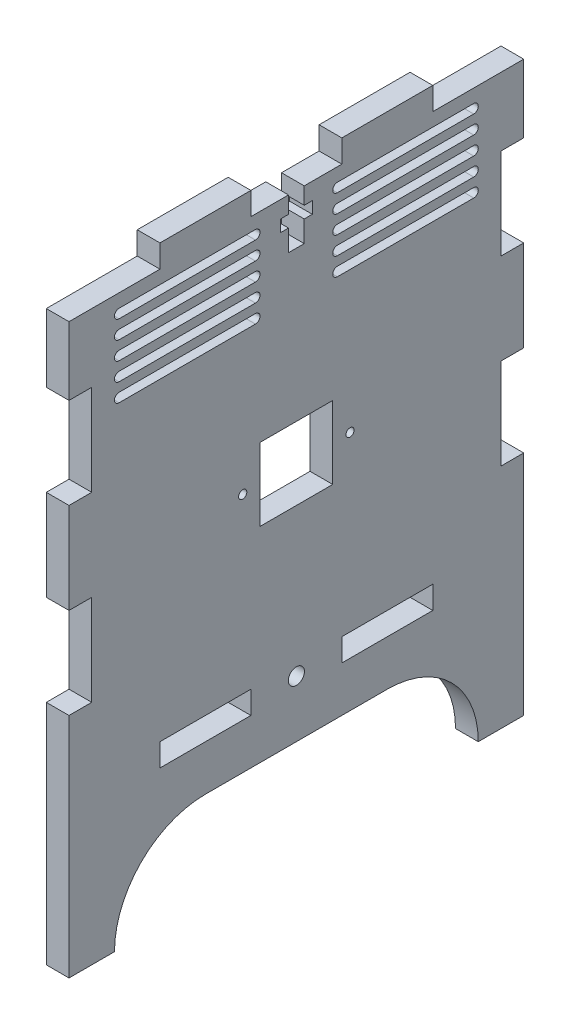
SolidWorks part; units mm, degrees
ref_plane "Front Plane" through (0, 0, 0) normal (0, 0, 1) x (1, 0, 0)
ref_plane "Top Plane" through (0, 0, 0) normal (0, 1, 0) x (1, 0, 0)
ref_plane "Right Plane" through (0, 0, 0) normal (1, 0, 0) x (0, 0, -1)
sketch "Sketch1" plane through (0, 0, 0) normal (1, 0, 0) x (0, 0, -1)
  line L1 (-63.5, 82.55) -> (63.5, 82.55)
  line L2 (-63.5, 82.55) -> (-63.5, -82.55)
  line L3 (-63.5, -82.55) -> (63.5, -82.55)
  line L4 (63.5, 82.55) -> (63.5, -82.55)
  line L5 (-63.5, 82.55) -> (63.5, -82.55) construction
  line L6 (-63.5, -82.55) -> (63.5, 82.55) construction
  point P0 (0, 0)
  dimension "D1" = 127
  dimension "D2" = 165.1
extrude "Boss-Extrude1" add sketch "Sketch1" along normal blind 6.35
sketch "Sketch2" plane through (6.35, 0, 0) normal (1, 0, 0) x (0, 0, -1)
  line L1 (-63.5, 82.55) -> (-38.1, 82.55)
  line L2 (-63.5, 82.55) -> (-63.5, 76.2)
  line L3 (-63.5, 76.2) -> (-38.1, 76.2)
  line L4 (-38.1, 82.55) -> (-38.1, 76.2)
  dimension "D1" = 25.4
  dimension "D2" = 6.35
extrude "Cut-Extrude1" cut sketch "Sketch2" against normal blind 6.35
pattern_linear "LPattern1" count 3 spacing 50.8 along (0, 0, -1) of "Cut-Extrude1"
sketch "Sketch5" plane through (6.35, 0, 0) normal (1, 0, 0) x (0, 0, -1)
  line L0 (-25.4, -82.55) -> (25.4, -82.55) construction
  line L1 (-63.5, -82.55) -> (63.5, -82.55) construction
  line L2 (-25.4, -57.15) -> (25.4, -57.15)
  line L3 (-25.4, -107.95) -> (25.4, -107.95)
  arc A0 (-25.4, -57.15) -> (-25.4, -107.95) centre (-25.4, -82.55) ccw
  arc A1 (25.4, -107.95) -> (25.4, -57.15) centre (25.4, -82.55) ccw
  point P4 (0, -82.55)
  dimension "D2" = 25.4
  dimension "D1" = 50.8
extrude "Cut-Extrude4" cut sketch "Sketch5" against normal blind 6.35
sketch "Sketch8" plane through (6.35, 0, 0) normal (1, 0, 0) x (0, 0, -1)
  line L0 (63.5, -82.55) -> (63.5, 76.2) construction
  line L1 (63.5, 57.15) -> (57.15, 57.15)
  line L2 (63.5, 57.15) -> (63.5, 31.75)
  line L3 (63.5, 31.75) -> (57.15, 31.75)
  line L4 (57.15, 57.15) -> (57.15, 31.75)
  line L5 (38.1, 82.55) -> (12.7, 82.55) construction
  dimension "D1" = 25.4
  dimension "D2" = 25.4
  dimension "D3" = 6.35
extrude "Cut-Extrude6" cut sketch "Sketch8" against normal blind 6.35
pattern_linear "LPattern4" count 2 spacing 50.8 along (0, -1, 0) of "Cut-Extrude6"
ref_plane "Plane1" through (0, 0, 0) normal (0, 0, 1) x (1, 0, 0)
mirror "Mirror1" about plane through (0, 0, 0) normal (0, 0, 1) of "LPattern4"
sketch "Sketch9" plane through (0, 0, 0) normal (-1, 0, 0) x (0, 0, 1)
  line L0 (-63.5, -82.55) -> (-63.5, -19.05) construction
  line L1 (-38.1, -38.1) -> (-12.7, -38.1)
  line L2 (-38.1, -38.1) -> (-38.1, -44.45)
  line L3 (-38.1, -44.45) -> (-12.7, -44.45)
  line L4 (-12.7, -38.1) -> (-12.7, -44.45)
  line L5 (-38.1, 82.55) -> (-12.7, 82.55) construction
  point P6 (-25.4, 82.55)
  dimension "D1" = 25.4
  dimension "D2" = 6.35
  dimension "D3" = 25.4
  dimension "D4" = 120.65
extrude "Cut-Extrude7" cut sketch "Sketch9" against normal blind 6.35
pattern_linear "LPattern6" count 2 spacing 50.8 along (0, 0, 1) of "Cut-Extrude7"
sketch "Sketch16" plane through (0, 0, 0) normal (-1, 0, 0) x (0, 0, 1)
  line L0 (12.7, 76.2) -> (-12.7, 76.2) construction
  line L1 (-2.1971, 76.2) -> (2.1971, 76.2)
  line L2 (-2.1971, 76.2) -> (-2.1971, 62.23)
  line L3 (-2.1971, 62.23) -> (2.1971, 62.23)
  line L4 (2.1971, 76.2) -> (2.1971, 62.23)
  line L5 (-12.7, 76.2) -> (-12.7, 82.55) construction
  line L7 (-4.445, 71.501) -> (4.445, 71.501)
  line L8 (-4.445, 71.501) -> (-4.445, 68.199)
  line L9 (-4.445, 68.199) -> (4.445, 68.199)
  line L10 (4.445, 71.501) -> (4.445, 68.199)
  point P6 (0, 62.23)
  point P13 (0, 71.501)
  point P14 (4.445, 69.85)
  dimension "D1" = 4.3942
  dimension "D2" = 13.97
  dimension "D3" = 12.7
  dimension "D4" = 3.302
  dimension "D5" = 8.89
  dimension "D6" = 12.7
  dimension "D7" = 6.35
extrude "Cut-Extrude14" cut sketch "Sketch16" against normal blind 6.35 contours L7 L10 L9 L8 | L1 L4 L3 L2
hole_wizard "#8 Clearance Hole1" positions "Sketch18" profile "Sketch17" hole size "#8" standard "ANSI Inch"
sketch "Sketch18" plane through (0, 0, 0) normal (-1, 0, 0) x (0, 0, 1)
  line L3 (-12.7, -44.45) -> (-12.7, -38.1) construction
  line L4 (38.1, -38.1) -> (12.7, -38.1) construction
  point P0 (0, -41.275)
  point P16 (-12.7, -41.275)
  dimension "D1" = 12.7
  dimension "D2" = 3.175
sketch "Sketch17" plane through (0, -41.275, 0) normal (0, 1, 0) x (0, 0, 1)
  line L0 (0, 0) -> (0, 11.5107)
  line L1 (0, 11.5107) -> (2.2479, 10.16)
  line L2 (2.2479, 10.16) -> (2.2479, 0)
  line L5 (2.2479, 0) -> (0, 0)
  line L10 (0, 11.5107) -> (-2.2479, 10.16) construction
  line L11 (0, -6.35) -> (0, 107.95) construction
  dimension "Hole Dia." = 4.4958
  dimension "Hole Depth" = 10.16
  dimension "Drill Angle" = 118
sketch "Sketch19" plane through (0, 0, 0) normal (-1, 0, 0) x (0, 0, 1)
  line L0 (-49.53, 71.1789) -> (-11.43, 71.1789) construction
  line L1 (-49.53, 72.4489) -> (-11.43, 72.4489)
  line L2 (-49.53, 69.9089) -> (-11.43, 69.9089)
  line L3 (-38.1, 82.55) -> (-38.1, 76.2) construction
  arc A0 (-49.53, 72.4489) -> (-49.53, 69.9089) centre (-49.53, 71.1789) ccw
  arc A1 (-11.43, 69.9089) -> (-11.43, 72.4489) centre (-11.43, 71.1789) ccw
  point P2 (-30.48, 71.1789)
  point P7 (-30.48, 72.4489)
  dimension "D2" = 1.27
  dimension "D1" = 38.1
  dimension "D3" = 7.62
extrude "Cut-Extrude15" cut sketch "Sketch19" against normal blind 6.35
mirror "Mirror2" about plane through (0, 0, 0) normal (0, 0, 1) of "Cut-Extrude15"
pattern_linear "LPattern7" count 5 spacing 5.08 along (0, -1, 0) of "Mirror2"
sketch "Sketch20" plane through (0, 0, 0) normal (-1, 0, 0) x (0, 0, 1)
  line L0 (-63.5, 6.35) -> (-63.5, 31.75) construction
  line L1 (-10.16, 20.32) -> (10.16, 20.32)
  line L2 (-10.16, 20.32) -> (-10.16, 0)
  line L3 (-10.16, 0) -> (10.16, 0)
  line L4 (10.16, 20.32) -> (10.16, 0)
  line L5 (38.1, -38.1) -> (12.7, -38.1) construction
  circle A0 centre (-14.986, 10.16) radius 1.143
  circle A1 centre (14.986, 10.16) radius 1.143
  point P4 (0, 0)
  point P11 (0, 20.32)
  point P12 (-10.16, 10.16)
  point P15 (10.16, 10.16)
  dimension "D6" = 2.286
  dimension "D7" = 2.286
  dimension "D8" = 14.986
  dimension "D1" = 20.32
  dimension "D2" = 20.32
  dimension "D3" = 63.5
  dimension "D4" = 38.1
  dimension "D5" = 14.986
extrude "Cut-Extrude16" cut sketch "Sketch20" against normal blind 10.16
